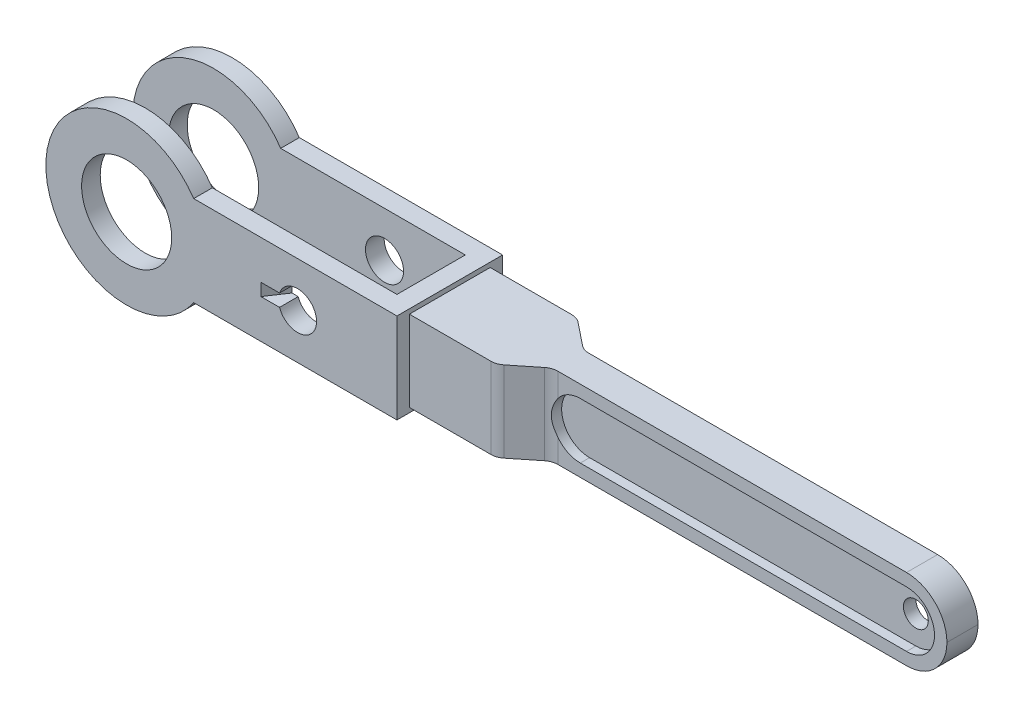
SolidWorks part; units mm, degrees
ref_plane "Plano frontal" through (0, 0, 0) normal (0, 0, 1) x (1, 0, 0)
ref_plane "Plano superior" through (0, 0, 0) normal (0, 1, 0) x (1, 0, 0)
ref_plane "Plano direito" through (0, 0, 0) normal (1, 0, 0) x (0, 0, -1)
sketch "Esboço1" plane through (0, 0, 0) normal (0, 0, 1) x (1, 0, 0)
  line L1 (21.5812, 14.5) -> (87, 14.5)
  line L2 (43.2107, 2) -> (43.2107, -2)
  line L3 (21.5812, -14.5) -> (87, -14.5)
  line L4 (87, 14.5) -> (87, -14.5)
  line L5 (43.2107, 2) -> (49.2107, 2)
  line L7 (49.2107, -2) -> (43.2107, -2)
  line L8 (43.2107, -2) -> (43.272, -1.9825)
  arc A0 (21.5812, 14.5) -> (21.5812, -14.5) centre (0, 0) ccw
  circle A1 centre (0, 0) radius 14.5
  arc A2 (49.2107, -2) -> (49.2107, 2) centre (55, 0) ccw
  dimension "D1" = 52
  dimension "D2" = 29
  dimension "D9" = 12.25
  dimension "D3" = 87
  dimension "D4" = 29
  dimension "D5" = 55
  dimension "D6" = 6
  dimension "D7" = 4
  dimension "D8" = 14.5
extrude "Ressalto-extrusão1" add sketch "Esboço1" along normal blind 34 contours L1 A0 L3 L4 A2 L7 L2 L5 A1 region at (29.8231, 0, 0)
sketch "Esboço2" plane through (0, 14.5, 0) normal (0, 1, 0) x (1, 0, 0)
  line L0 (21.5812, 0) -> (87, 0) construction
  line L1 (-34.2799, -6) -> (81, -6)
  line L2 (-34.2799, -6) -> (-34.2799, -28)
  line L3 (-34.2799, -28) -> (81, -28)
  line L4 (81, -6) -> (81, -28)
  line L5 (21.5812, -34) -> (87, -34) construction
  line L6 (87, -34) -> (87, 0) construction
  dimension "D1" = 6
  dimension "D2" = 6
  dimension "D3" = 6
extrude "Corte-extrusão1" cut sketch "Esboço2" against normal blind 56 and the other way blind 36
sketch "Esboço3" plane through (0, -2, 0) normal (0, 1, 0) x (1, 0, 0)
  line L0 (43.2107, -28) -> (47.2107, -28)
  line L1 (43.2107, -28) -> (49.2107, -28) construction
  line L2 (47.2107, -28) -> (43.2107, -34)
  line L3 (43.2107, -34) -> (43.2107, -28)
  dimension "D1" = 2
  dimension "D2" = 6
extrude "Ressalto-extrusão2" add sketch "Esboço3" along normal up to surface (4 mm away) up to face at (46.2107, 2, 31)
sketch "Esboço4" plane through (0, 0, 6) normal (0, 0, 1) x (1, 0, 0)
  line L0 (42.9359, 2) -> (49.2107, 2)
  line L2 (42.9359, 2) -> (42.8723, -2)
  line L3 (49.2107, -2) -> (42.8723, -2)
  line L5 (42.8723, -2) -> (42.8723, -2.0365)
  arc A0 (49.2107, 2) -> (49.2107, -2) centre (55, 0) ccw
  line M2 (49.2107, -2) -> (43.2107, -2)
  line M3 (43.2107, -2) -> (43.2107, 2)
  line M4 (43.2107, 2) -> (49.2107, 2)
extrude "Ressalto-extrusão3" add sketch "Esboço4" against normal up to vertex (6 mm away) contours A0 M4 M3 M2 region at (46.0991, 0, 6) up to point (43.2107, 2, 0)
sketch "Esboço5" plane through (87, 0, 0) normal (1, 0, 0) x (0, 0, -1)
  line L0 (-34, 14.5) -> (-34, -14.5) construction
  line L1 (-30, 13) -> (-4, 13)
  line L2 (-30, 13) -> (-30, -13)
  line L3 (-30, -13) -> (-4, -13)
  line L4 (-4, 13) -> (-4, -13)
  line L5 (0, 14.5) -> (0, -14.5) construction
  line L6 (-34, -14.5) -> (0, -14.5) construction
  line L7 (-34, 14.5) -> (0, 14.5) construction
  dimension "D1" = 4
  dimension "D2" = 4
  dimension "D3" = 26
  dimension "D5" = 26
  dimension "D6" = 1.5
  dimension "D7" = 1.5
extrude "Ressalto-extrusão4" add sketch "Esboço5" along normal blind 28
sketch "Esboço6" plane through (81, 0, 0) normal (-1, 0, 0) x (0, 0, 1)
  circle A0 centre (17, 0) radius 9
  dimension "D1" = 18
extrude "Corte-extrusão2" cut sketch "Esboço6" against normal blind 31
sketch "Esboço7" plane through (115, 0, 0) normal (1, 0, 0) x (0, 0, -1)
  line L0 (-4, 13) -> (-30, 13) construction
  line L1 (-22, 13) -> (-12, 13)
  line L2 (-22, 13) -> (-22, -13)
  line L3 (-22, -13) -> (-12, -13)
  line L4 (-12, 13) -> (-12, -13)
  line L5 (-30, -13) -> (-4, -13) construction
  line L6 (-30, 13) -> (-30, -13) construction
  dimension "D1" = 10
  dimension "D2" = 8
extrude "Ressalto-extrusão5" add sketch "Esboço7" along normal blind 10
sketch "Esboço8" plane through (0, 13, 0) normal (0, 1, 0) x (1, 0, 0)
  line L0 (115, -4) -> (115, -30)
  line L1 (115, -30) -> (125, -22)
  line L2 (125, -22) -> (125, -12)
  line L3 (125, -12) -> (115, -4)
  line L4 (115, -4) -> (114.9707, -4.1681)
  line M3 (115, -30) -> (115, -22)
  line M4 (115, -22) -> (125, -22)
  line M5 (125, -22) -> (125, -12)
  line M6 (125, -12) -> (115, -12)
  line M7 (115, -12) -> (115, -4)
extrude "Ressalto-extrusão7" add sketch "Esboço8" against normal up to vertex (26 mm away) contours L0 M6 M4 M5 | L1 M3 M4 | L3 M6 M7 region at (118.3333, 13, 9.3333) region at (120, 13, 17) region at (118.3333, 13, 24.6667) up to point (125, -13, 22)
fillet "Filete1" radius 5 2 edges at (115, 0, 4) (115, 0, 30)
sketch "Esboço9" plane through (125, 0, 0) normal (1, 0, 0) x (0, 0, -1)
  line L1 (-22, 13) -> (-12, 13)
  line L2 (-22, 13) -> (-22, -13)
  line L3 (-22, -13) -> (-12, -13)
  line L4 (-12, 13) -> (-12, -13)
extrude "Ressalto-extrusão8" add sketch "Esboço9" along normal blind 127
fillet "Filete2" radius 13 2 edges at (252, -13, 17) (252, 13, 17)
fillet "Filete3" radius 5 2 edges at (125, 0, 12) (125, 0, 22)
sketch "Esboço10" plane through (0, 0, 22) normal (0, 0, 1) x (1, 0, 0)
  line L0 (134, 0) -> (239, 0) construction
  line L1 (134, 9) -> (239, 9)
  line L2 (134, -9) -> (239, -9)
  arc A0 (134, 9) -> (134, -9) centre (134, 0) ccw
  arc A1 (239, -9) -> (239, 9) centre (239, 0) ccw
  point P3 (186.5, 0)
  dimension "D2" = 9
  dimension "D1" = 105
  dimension "D3" = 0
extrude "Corte-extrusão3" cut sketch "Esboço10" against normal blind 3 and the other way blind 49
sketch "Esboço11" plane through (0, 0, 12) normal (0, 0, -1) x (-1, 0, 0)
  line L0 (-239, 0) -> (-134, 0) construction
  line L1 (-239, 9) -> (-134, 9)
  line L2 (-239, -9) -> (-134, -9)
  arc A0 (-239, 9) -> (-239, -9) centre (-239, 0) ccw
  arc A1 (-134, -9) -> (-134, 9) centre (-134, 0) ccw
  point P4 (-186.5, 0)
  dimension "D1" = 9
extrude "Corte-extrusão4" cut sketch "Esboço11" against normal blind 3 and the other way blind 52
sketch "Esboço12" plane through (0, 0, 15) normal (0, 0, -1) x (-1, 0, 0)
  circle A0 centre (-239, 0) radius 4
  dimension "D1" = 8
extrude "Corte-extrusão5" cut sketch "Esboço12" against normal blind 22 and the other way blind 27
